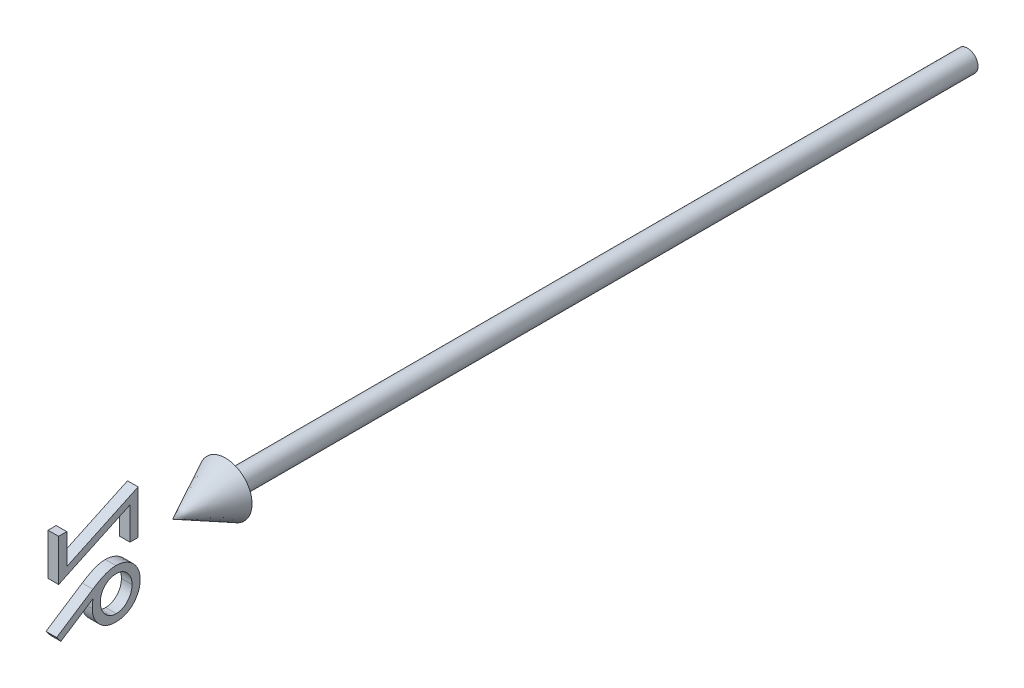
SolidWorks part; units mm, degrees
ref_plane "Front Plane" through (0, 0, 0) normal (0, 0, 1) x (1, 0, 0)
ref_plane "Top Plane" through (0, 0, 0) normal (0, 1, 0) x (1, 0, 0)
ref_plane "Right Plane" through (0, 0, 0) normal (1, 0, 0) x (0, 0, -1)
sketch "Sketch2" plane through (0, 0, 0) normal (0, 1, 0) x (1, 0, 0)
  line L0 (0, 41.95) -> (0, -114.4521) construction
  line L1 (-36.8894, 0) -> (41.4965, 0) construction
  line L2 (0, -150) -> (5, -140)
  line L3 (5, -140) -> (2, -140)
  line L4 (2, -140) -> (2, 0)
  line L5 (2, 0) -> (0, 0)
  line L6 (0, 0) -> (0, -150)
  dimension "D1" = 150
  dimension "D2" = 2
  dimension "D3" = 10
  dimension "D4" = 5
revolve "Revolve1" add sketch "Sketch2" angle 360 about L0
sketch "Sketch3" plane through (0, 0, 0) normal (1, 0, 0) x (0, -1, 0)
  line L0 (0, -101.5706) -> (0, -127.8138) construction
  line L1 (-10.1124, -157.5) -> (14.1256, -157.5) construction
  line L2 (-26.0511, 0) -> (25.2792, 0) construction
  text T0 "Z6\r\n" font "Century Gothic" height 15
  dimension "D1" = 157.5
extrude "Boss-Extrude1" add sketch "Sketch3" against normal blind 1 and the other way blind 1 separate body
equation "\"D1@Sketch2\"=\"frame_arrow_length\""
equation "\"D2@Sketch2\"=\"frame_arrow_odA\"/2"
equation "\"D4@Sketch2\"=\"frame_arrow_head_od\""
equation "\"D3@Sketch2\"=\"frame_arrow_head_length\""
equation "\"frame_arrow_length\"=150"
equation "\"frame_arrow_head_length\"=10"
equation "\"frame_arrow_head_od\"=5"
equation "\"frame_arrow_odA\"=4"
equation "\"D1@Sketch3\"=\"frame_arrow_length\"*1.05"
